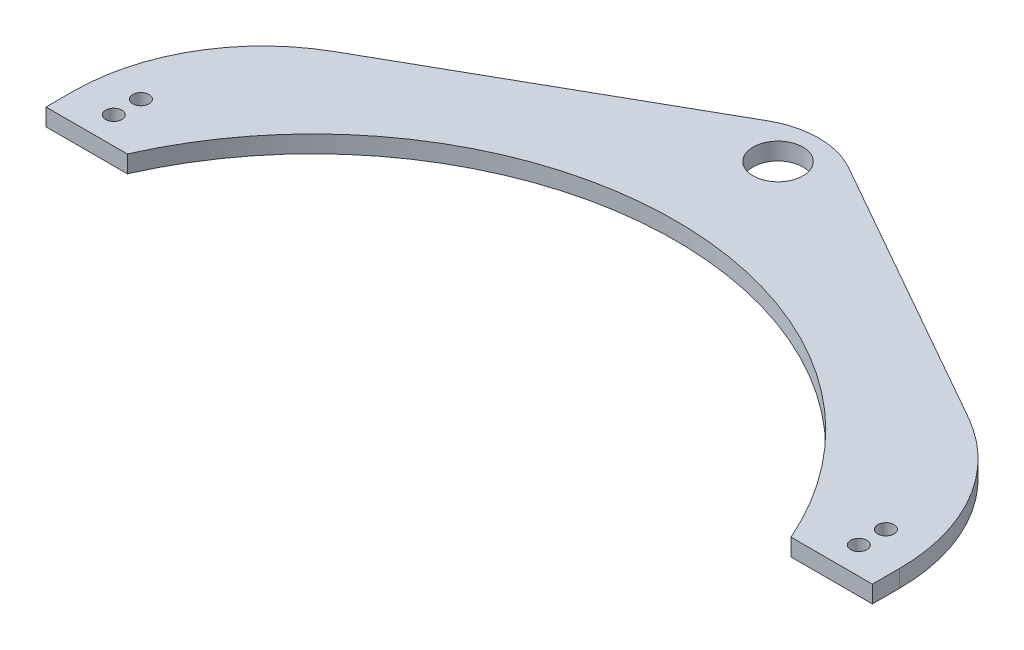
SolidWorks part; units mm, degrees
ref_plane "Front Plane" through (0, 0, 0) normal (0, 0, 1) x (1, 0, 0)
ref_plane "Top Plane" through (0, 0, 0) normal (0, 1, 0) x (1, 0, 0)
ref_plane "Right Plane" through (0, 0, 0) normal (1, 0, 0) x (0, 0, -1)
sketch "Sketch1" plane through (0, 0, 0) normal (0, 1, 0) x (1, 0, 0)
  line L0 (0, 0) -> (122.4, 0)
  line L1 (61.2, 0) -> (61.2, 39.9)
  line L2 (122.4, 0) -> (137.4, 0)
  line L3 (0, 0) -> (-15, 0)
  line L4 (137.4, 0) -> (137.4, 16.6577)
  line L5 (-15, 0) -> (-15, 16.6577)
  line L6 (61.2, 0) -> (61.2, 58.8)
  line L7 (61.2, 58.8) -> (61.2, 66.3)
  line L8 (61.2, 66.3) -> (61.2465, 66.3)
  line L9 (61.2, 66.3) -> (61.1535, 66.3)
  line L10 (68.6399, 64.3514) -> (129.7934, 29.709)
  line L11 (53.7601, 64.3514) -> (-7.3934, 29.709)
  line L12 (129.9, 0) -> (129.9, 5)
  line L13 (129.9, 5) -> (129.9, 10)
  line L14 (-7.5, 0) -> (-7.5, 10)
  line L15 (119.6512, 35.4544) -> (68.6399, 64.3514)
  line L16 (137.4, 5.0012) -> (137.4, 0)
  line L17 (53.7601, 64.3514) -> (2.7488, 35.4544)
  line L18 (-15, 5.0012) -> (-15, 0)
  arc A0 (0, 0) -> (122.4, 0) centre (61.2, -26.9726) cw
  circle A1 centre (61.2, 58.8) radius 4.6
  arc A2 (61.2465, 66.3) -> (68.6399, 64.3514) centre (61.2465, 51.3) cw
  arc A3 (61.1535, 66.3) -> (53.7601, 64.3514) centre (61.1535, 51.3) ccw
  arc A4 (-15, 16.6577) -> (-7.3934, 29.709) centre (0, 16.6577) cw
  arc A5 (137.4, 16.6577) -> (129.7934, 29.709) centre (122.4, 16.6577) ccw
  circle A6 centre (129.9, 10) radius 1.5
  circle A7 centre (129.9, 5) radius 1.5
  circle A8 centre (-7.5, 10) radius 1.5
  circle A9 centre (-7.5, 5) radius 1.5
  arc A10 (119.6512, 35.4544) -> (137.4, 5.0012) centre (102.4, 5.0012) cw
  arc A11 (2.7488, 35.4544) -> (-15, 5.0012) centre (20, 5.0012) ccw
  point P17 (65.2, 66.3)
  point P20 (57.2, 66.3)
  point P23 (-15, 25.4)
  point P26 (137.4, 25.4)
  point P41 (137.4, 25.4)
  point P44 (-15, 25.4)
  dimension "D8" = 7.5
  dimension "D11" = 15
  dimension "D12" = 15
  dimension "D15" = 10
  dimension "D16" = 35
  dimension "D1" = 122.4
  dimension "D2" = 39.9
  dimension "D3" = 15
  dimension "D4" = 15
  dimension "D5" = 25.4
  dimension "D6" = 25.4
  dimension "D7" = 58.8
  dimension "D9" = 4
  dimension "D10" = 4
  dimension "D13" = 5
  dimension "D14" = 5
extrude "Boss-Extrude2" add sketch "Sketch1" along normal blind 3.175 contours L11 A11 L5 L3 A9 A8 A0 L6 A1 L7 L9 A3 | A10 L10 A2 L8 L7 A1 L6 A0 L2 A7 A6 L4 region at (21.8428, 0, -33.5541) region at (100.5572, 0, -33.5541)
